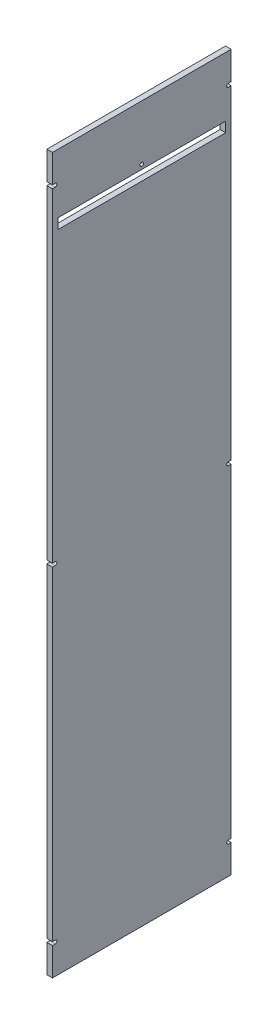
SolidWorks part; units mm, degrees
ref_plane "Front Plane" through (0, 0, 0) normal (0, 0, 1) x (1, 0, 0)
ref_plane "Top Plane" through (0, 0, 0) normal (0, 1, 0) x (1, 0, 0)
ref_plane "Right Plane" through (0, 0, 0) normal (1, 0, 0) x (0, 0, -1)
sketch "Sketch1" plane through (0, 0, 0) normal (0, 1, 0) x (1, 0, 0)
  line L1 (0, 0) -> (4.7625, 0)
  line L2 (0, 0) -> (0, 152.4)
  line L3 (0, 152.4) -> (4.7625, 152.4)
  line L4 (4.7625, 0) -> (4.7625, 152.4)
  dimension "D1" = 152.4
  dimension "D2" = 4.7625
extrude "Boss-Extrude1" add sketch "Sketch1" along normal blind 609.6
sketch "Sketch2" plane through (4.7625, 0, 0) normal (1, 0, 0) x (0, 0, -1)
  line L1 (147.6375, 558.8) -> (4.7625, 558.8)
  line L2 (147.6375, 558.8) -> (147.6375, 550.418)
  line L3 (147.6375, 550.418) -> (4.7625, 550.418)
  line L4 (4.7625, 558.8) -> (4.7625, 550.418)
extrude "Cut-Extrude1" cut sketch "Sketch2" against normal through all
sketch "Sketch3" plane through (0, 0, 0) normal (-1, 0, 0) x (0, 0, 1)
  line L0 (-2.3813, 0) -> (-2.3813, 23.9395) construction
  line L1 (-152.4, 0) -> (0, 0) construction
  line L2 (-152.4, 609.6) -> (0, 609.6) construction
  line L3 (-150.0188, 0) -> (-150.0188, 23.9395) construction
  line L4 (0, 609.6) -> (0, 0) construction
  line L5 (-152.4, 609.6) -> (-152.4, 0) construction
  line L6 (0, 584.2) -> (-152.4, 584.2) construction
  line L7 (0, 25.4) -> (-152.4, 25.4) construction
  line L8 (0, 304.8) -> (-152.4, 304.8) construction
  line L9 (-2.3813, 582.7395) -> (0, 582.7395)
  line L10 (-2.3813, 585.6605) -> (0, 585.6605)
  line L11 (-150.0188, 585.6605) -> (-152.4, 585.6605)
  line L12 (-150.0188, 582.7395) -> (-152.4, 582.7395)
  line L13 (-150.0188, 303.3395) -> (-152.4, 303.3395)
  line L14 (-150.0188, 306.2605) -> (-152.4, 306.2605)
  line L15 (-2.3813, 303.3395) -> (0, 303.3395)
  line L16 (-2.3813, 306.2605) -> (0, 306.2605)
  line L17 (-152.4, 303.3395) -> (-152.4, 306.2605)
  line L18 (-2.3813, 23.9395) -> (0, 23.9395)
  line L20 (-2.3813, 26.8605) -> (0, 26.8605)
  line L21 (0, 23.9395) -> (0, 26.8605)
  line L22 (-150.0188, 23.9395) -> (-152.4, 23.9395)
  line L23 (-2.3813, 26.8605) -> (-2.3813, 609.6) construction
  line L24 (-150.0188, 26.8605) -> (-152.4, 26.8605)
  line L25 (-152.4, 23.9395) -> (-152.4, 26.8605)
  line L26 (-152.4, 582.7395) -> (-152.4, 585.6605)
  line L27 (0, 582.7395) -> (0, 585.6605)
  line L28 (0, 303.3395) -> (0, 306.2605)
  line L30 (-150.0188, 26.8605) -> (-150.0188, 609.6) construction
  arc A0 (-2.3813, 26.8605) -> (-2.3813, 23.9395) centre (-2.3813, 25.4) ccw
  arc A1 (-150.0188, 23.9395) -> (-150.0188, 26.8605) centre (-150.0188, 25.4) ccw
  arc A2 (-150.0188, 303.3395) -> (-150.0188, 306.2605) centre (-150.0188, 304.8) ccw
  arc A3 (-150.0188, 582.7395) -> (-150.0188, 585.6605) centre (-150.0188, 584.2) ccw
  arc A4 (-2.3813, 585.6605) -> (-2.3813, 582.7395) centre (-2.3813, 584.2) ccw
  arc A5 (-2.3813, 306.2605) -> (-2.3813, 303.3395) centre (-2.3813, 304.8) ccw
  dimension "D5" = 2.921
  dimension "D1" = 2.3813
  dimension "D2" = 2.3813
  dimension "D3" = 25.4
  dimension "D4" = 25.4
extrude "Cut-Extrude2" cut sketch "Sketch3" against normal through all
hole_wizard "#4 Clearance Hole1" positions "Sketch4" profile "Sketch5" hole size "#4" standard "ANSI Inch" end condition through all
sketch "Sketch4" plane through (0, 0, 0) normal (-1, 0, 0) x (0, 0, 1)
  line L0 (0, 562.7688) -> (-152.4, 562.7688) construction
  line L1 (0, 582.7395) -> (0, 306.2605) construction
  line L2 (-152.4, 582.7395) -> (-152.4, 306.2605) construction
  line L4 (-147.6375, 558.8) -> (-4.7625, 558.8) construction
  point P11 (-76.2, 562.7688)
  dimension "D1" = 3.9688
sketch "Sketch5" plane through (0, 562.7688, -76.2) normal (0, 1, 0) x (0, 0, 1)
  line L0 (0, 0) -> (0, 4.7625)
  line L1 (0, 4.7625) -> (1.4732, 4.7625)
  line L2 (1.4732, 4.7625) -> (1.4732, 0)
  line L5 (1.4732, 0) -> (0, 0)
  line L11 (0, -6.35) -> (0, 107.95) construction
  dimension "Thru Hole Dia." = 2.9464
  dimension "Thru Hole Depth" = 4.7625
sketch "Sketch6" plane through (0, 0, 0) normal (-1, 0, 0) x (0, 0, 1)
  line L0 (-147.6375, 550.418) -> (-147.6375, 558.8) construction
  line L1 (-147.6375, 558.8) -> (-4.7625, 558.8) construction
  line L2 (-4.7625, 558.8) -> (-4.7625, 550.418) construction
  line L3 (-4.7625, 550.418) -> (-147.6375, 550.418) construction
  line L4 (-147.6375, 550.418) -> (-147.6375, 558.8)
  line L5 (-147.6375, 558.8) -> (-4.7625, 558.8)
  line L6 (-4.7625, 558.8) -> (-4.7625, 550.418)
  line L7 (-4.7625, 550.418) -> (-147.6375, 550.418)
  line L8 (-147.7645, 550.291) -> (-147.7645, 558.927)
  line L9 (-147.7645, 558.927) -> (-4.6355, 558.927)
  line L10 (-4.6355, 558.927) -> (-4.6355, 550.291)
  line L11 (-4.6355, 550.291) -> (-147.7645, 550.291)
  dimension "D1" = 0.127
extrude "Cut-Extrude3" cut sketch "Sketch6" against normal through all
